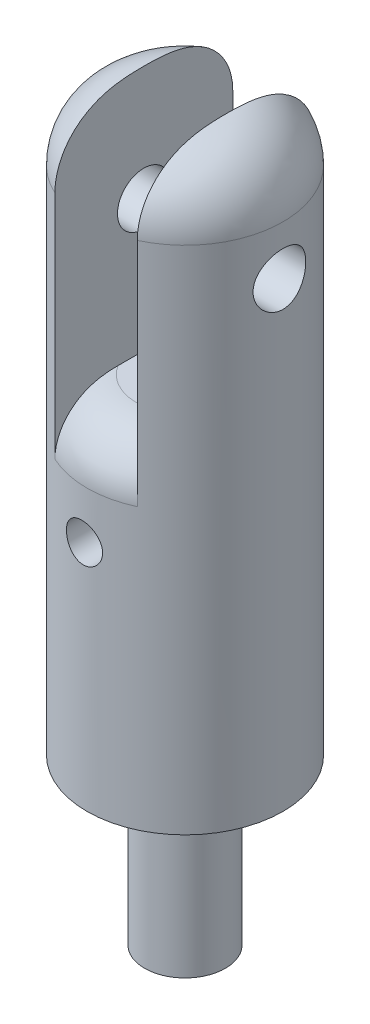
SolidWorks part; units mm, degrees
material "Alloy Steel (SS)"
ref_plane "Front Plane" through (0, 0, 0) normal (0, 0, 1) x (1, 0, 0)
ref_plane "Top Plane" through (0, 0, 0) normal (0, 1, 0) x (1, 0, 0)
ref_plane "Right Plane" through (0, 0, 0) normal (1, 0, 0) x (0, 0, -1)
sketch "Sketch1" plane through (0, 0, 0) normal (0, 1, 0) x (1, 0, 0)
  circle A0 centre (0, 0) radius 2.45
  dimension "D1" = 4.9
extrude "Boss-Extrude1" add sketch "Sketch1" along normal blind 10
sketch "Sketch2" plane through (0, 10, 0) normal (0, 1, 0) x (1, 0, 0)
  circle A0 centre (0, 0) radius 5.95
  dimension "D1" = 11.9
extrude "Boss-Extrude2" add sketch "Sketch2" along normal blind 35
sketch "Sketch4" plane through (0, 0, 0) normal (1, 0, 0) x (0, 0, -1)
  line L0 (5.95, 10) -> (5.95, 45) construction
  line L1 (-5.95, 45) -> (5.95, 45)
  line L2 (-5.95, 45) -> (-5.95, 30)
  line L3 (-5.95, 30) -> (5.95, 30)
  line L4 (5.95, 45) -> (5.95, 30)
  dimension "D1" = 15
extrude "Cut-Extrude1" cut sketch "Sketch4" against normal mid plane 5
sketch "Sketch5" plane through (0, 0, 0) normal (1, 0, 0) x (0, 0, -1)
  line L0 (5.3993, 45) -> (-5.3993, 45) construction
  circle A0 centre (0, 38) radius 1.6
  dimension "D1" = 3.2
  dimension "D2" = 7
extrude "Cut-Extrude2" cut sketch "Sketch5" against normal through all both and the other way through all
fillet "Fillet1" radius 4 2 edges at (5.95, 45, 0) (-5.95, 45, 0)
fillet "Fillet2" radius 3 2 edges at (0, 30, -5.95) (0, 30, 5.95)
ref_plane "Plane1" through (-0.0118, 0, 5.95) normal (-0.002, 0, 1) x (1, 0, 0.002)
sketch "Sketch6" plane through (-0.0118, 0, 5.95) normal (-0.002, 0, 1) x (1, 0, 0.002)
  line L1 (-0.2584, 22) -> (-0.2584, 24) construction
  circle A0 centre (-0.2584, 24) radius 1.15
  point P2 (0, 0)
  dimension "D1" = 2.3
  dimension "D2" = 2
extrude "Cut-Extrude3" cut sketch "Sketch6" against normal blind 15
